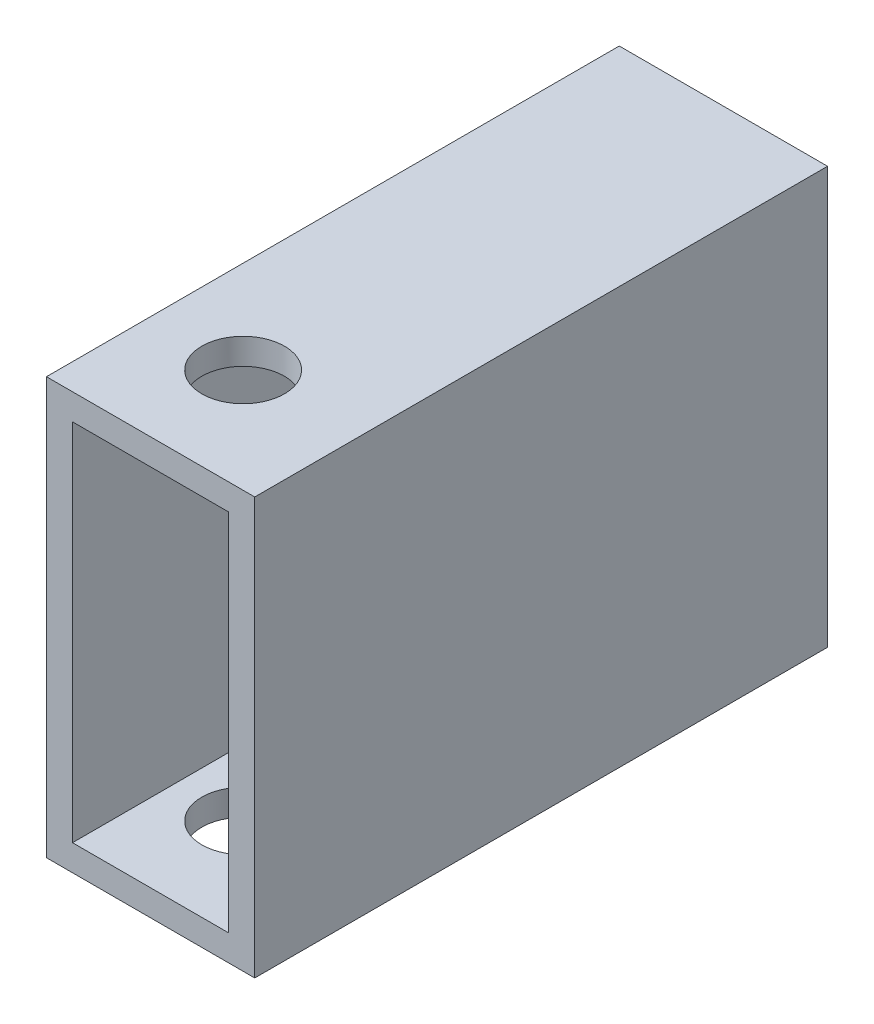
SolidWorks part; units mm, degrees
ref_plane "Front Plane" through (0, 0, 0) normal (0, 0, 1) x (1, 0, 0)
ref_plane "Top Plane" through (0, 0, 0) normal (0, 1, 0) x (1, 0, 0)
ref_plane "Right Plane" through (0, 0, 0) normal (1, 0, 0) x (0, 0, -1)
sketch "Sketch1" plane through (0, 0, 0) normal (0, 0, 1) x (1, 0, 0)
  line L1 (-19.9893, 31.9003) -> (5.4107, 31.9003)
  line L2 (-19.9893, 31.9003) -> (-19.9893, -18.8997)
  line L3 (-19.9893, -18.8997) -> (5.4107, -18.8997)
  line L4 (5.4107, 31.9003) -> (5.4107, -18.8997)
  line L5 (-19.9893, 31.9003) -> (5.4107, -18.8997) construction
  line L6 (-19.9893, -18.8997) -> (5.4107, 31.9003) construction
  line L7 (2.2357, 28.7253) -> (-16.8143, 28.7253)
  line L8 (2.2357, 28.7253) -> (2.2357, -15.7247)
  line L9 (2.2357, -15.7247) -> (-16.8143, -15.7247)
  line L10 (-16.8143, 28.7253) -> (-16.8143, -15.7247)
  point P0 (-7.2893, 6.5003)
  dimension "D1" = 25.4
  dimension "D2" = 50.8
  dimension "D3" = 3.175
  dimension "D4" = 3.175
  dimension "D5" = 3.175
  dimension "D6" = 3.175
extrude "Boss-Extrude1" add sketch "Sketch1" along normal blind 69.85
sketch "Sketch4" plane through (0, 31.9003, 0) normal (0, 1, 0) x (1, 0, 0)
  line L0 (5.4107, -69.85) -> (-19.9893, -69.85) construction
  circle A0 centre (-8.7053, -57.15) radius 5.0419
  dimension "D1" = 10.0838
  dimension "D2" = 12.7
extrude "Cut-Extrude2" cut sketch "Sketch4" against normal up to surface (50.8 mm away) up to face at (-7.2893, -18.8997, 34.925)
